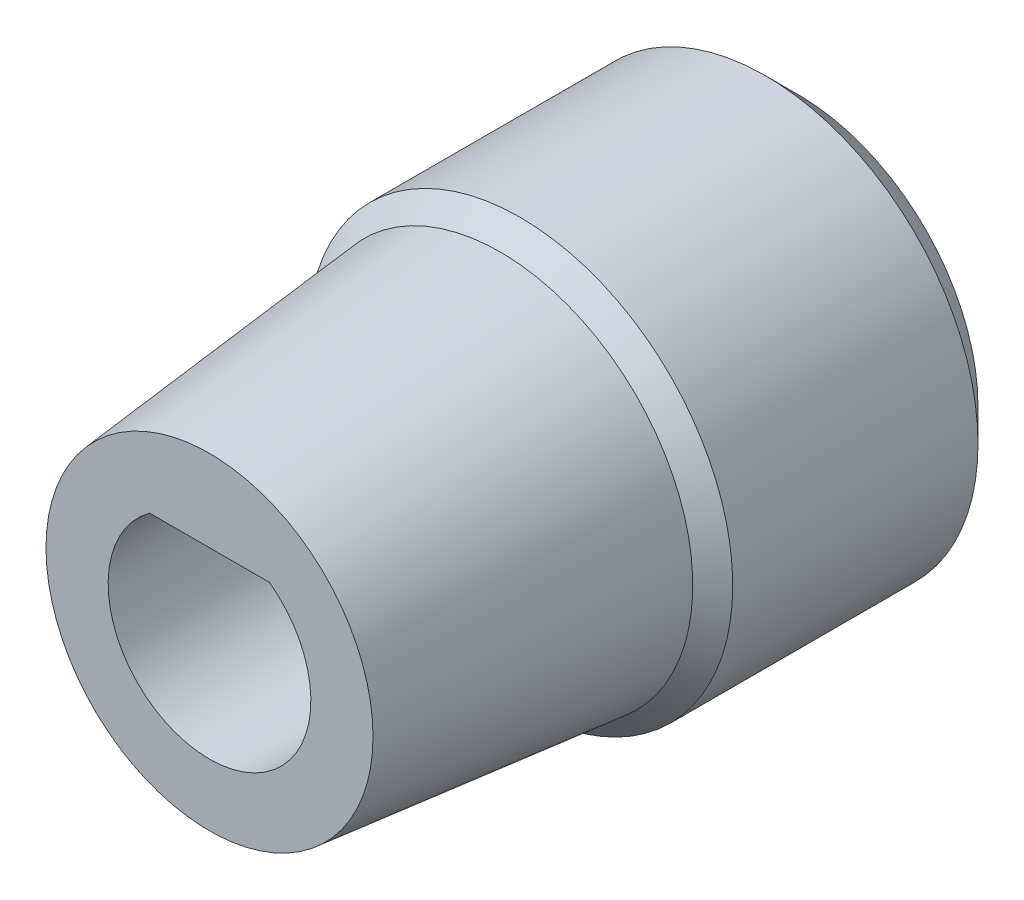
SolidWorks part; units mm, degrees
ref_plane "Front Plane" through (0, 0, 0) normal (0, 0, 1) x (1, 0, 0)
ref_plane "Top Plane" through (0, 0, 0) normal (0, 1, 0) x (1, 0, 0)
ref_plane "Right Plane" through (0, 0, 0) normal (1, 0, 0) x (0, 0, -1)
sketch "Sketch1" plane through (0, 0, 0) normal (0, 0, 1) x (1, 0, 0)
  line L0 (-1.833, 2.5) -> (1.833, 2.5)
  circle A0 centre (0, 0) radius 4.5
  circle A1 centre (0, 0) radius 3.1
  circle A2 centre (0, 0) radius 6
  circle A3 centre (0, 0) radius 6.5
  dimension "D1" = 9
  dimension "D2" = 6.2
  dimension "D4" = 12
  dimension "D5" = 13
  dimension "D3" = 2.5
extrude "Boss-Extrude1" add sketch "Sketch1" along normal blind 10 contours A2 A1 | L0 A1 | A2 A0 region at (0, 2.7421, 0) region at (-4.3727, 0, 0) region at (-5.8303, 0, 0)
extrude "Boss-Extrude2" add sketch "Sketch1<3>" along normal blind 3 contours A2 A1 | A1 region at (-4.3727, 0, 0)
sketch "Sketch1<3>" plane through (0, 0, 0) normal (0, 0, 1) x (1, 0, 0) same geometry as "Sketch1"
extrude "Boss-Extrude3" add sketch "Sketch1<6>" against normal blind 8 contours A3 A0 | A2 A0 region at (-5.8303, 0, 0) region at (-6.3162, 0, 0)
sketch "Sketch1<6>" plane through (0, 0, 0) normal (0, 0, 1) x (1, 0, 0) same geometry as "Sketch1"
chamfer "Chamfer1" distance 1 distance2 1 1 edges at (6, 0, 0)
chamfer "Chamfer2" distance 10 distance2 1 1 edges at (6, 0, 10) first distance on face at (6, 0, 1)
chamfer "Chamfer3" distance 1 angle 45 1 edges at (6.5, 0, -8)
thread "Thread1" pitch 1.5 method cut profile "Thread Profile1" start angle 0, offset 1, length 0, pitch 1.5, diameter 9
ref_plane "Plane1" through (4.5, 0, -9) normal (0, -1, 0) x (1, 0, 0)
sketch "Thread Profile1" plane through (4.5, 0, -9) normal (0, -1, 0) x (1, 0, 0)
  line L0 (0, 0) -> (0, 1.5) construction
  line L1 (0, 0) -> (0.8119, 0.4687)
  line L2 (0.8119, 0.4687) -> (0.8119, 0.6562)
  line L3 (0.8119, 0.6562) -> (0, 1.125)
  line L4 (0.8119, 0.5625) -> (0, 0.5625) construction
  line L11 (0, 0) -> (0, 1.125)
  point P2 (0, 0)
  dimension "Pitch" = 1.5
  dimension "Profile_Angle" = 60
  dimension "Profile_Land" = 0.1875
  dimension "Profile_Height" = 0.8119
